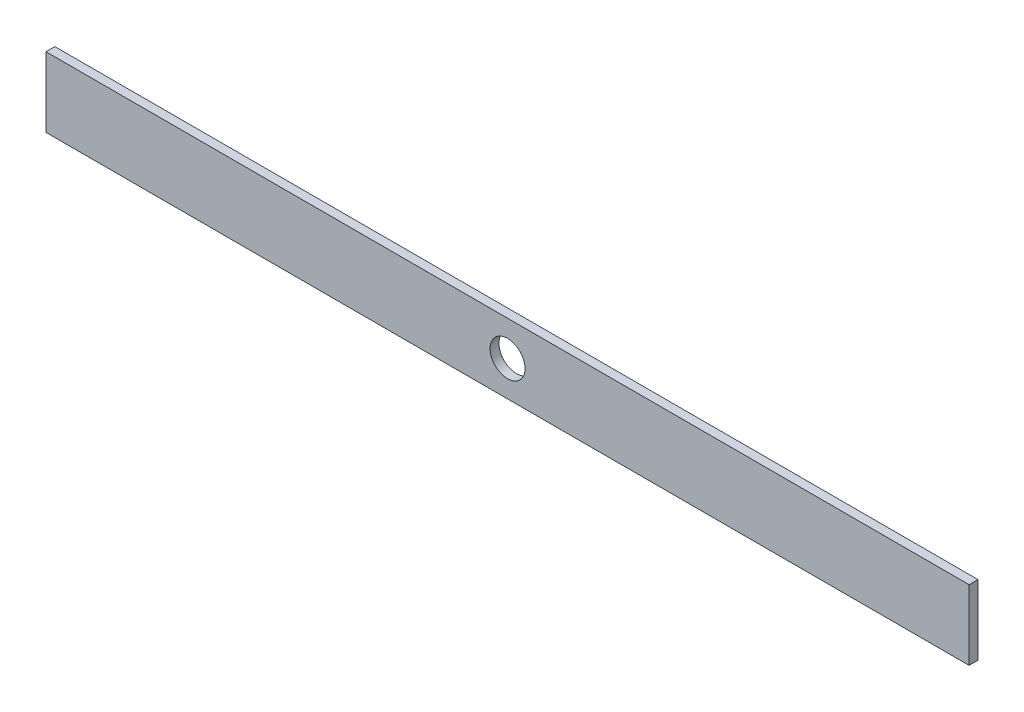
SolidWorks part; units mm, degrees
material "Acrylic (Medium-high impact)"
ref_plane "Front Plane" through (0, 0, 0) normal (0, 0, 1) x (1, 0, 0)
ref_plane "Top Plane" through (0, 0, 0) normal (0, 1, 0) x (1, 0, 0)
ref_plane "Right Plane" through (0, 0, 0) normal (1, 0, 0) x (0, 0, -1)
sketch "Sketch1" plane through (0, 0, 0) normal (0, 0, 1) x (1, 0, 0)
  line L1 (-330.2, -25) -> (330.2, -25)
  line L2 (-330.2, -25) -> (-330.2, 25)
  line L3 (-330.2, 25) -> (330.2, 25)
  line L4 (330.2, -25) -> (330.2, 25)
  line L5 (-330.2, -25) -> (330.2, 25) construction
  line L6 (-330.2, 25) -> (330.2, -25) construction
  point P0 (0, 0)
  dimension "D1" = 660.4
  dimension "D2" = 50
extrude "Boss-Extrude1" add sketch "Sketch1" along normal blind 6.35
sketch "Sketch2" plane through (0, 0, 0) normal (0, 0, -1) x (-1, 0, 0)
  circle A0 centre (0, 0) radius 12.5
  dimension "D1" = 25
extrude "Cut-Extrude1" cut sketch "Sketch2" against normal through all
